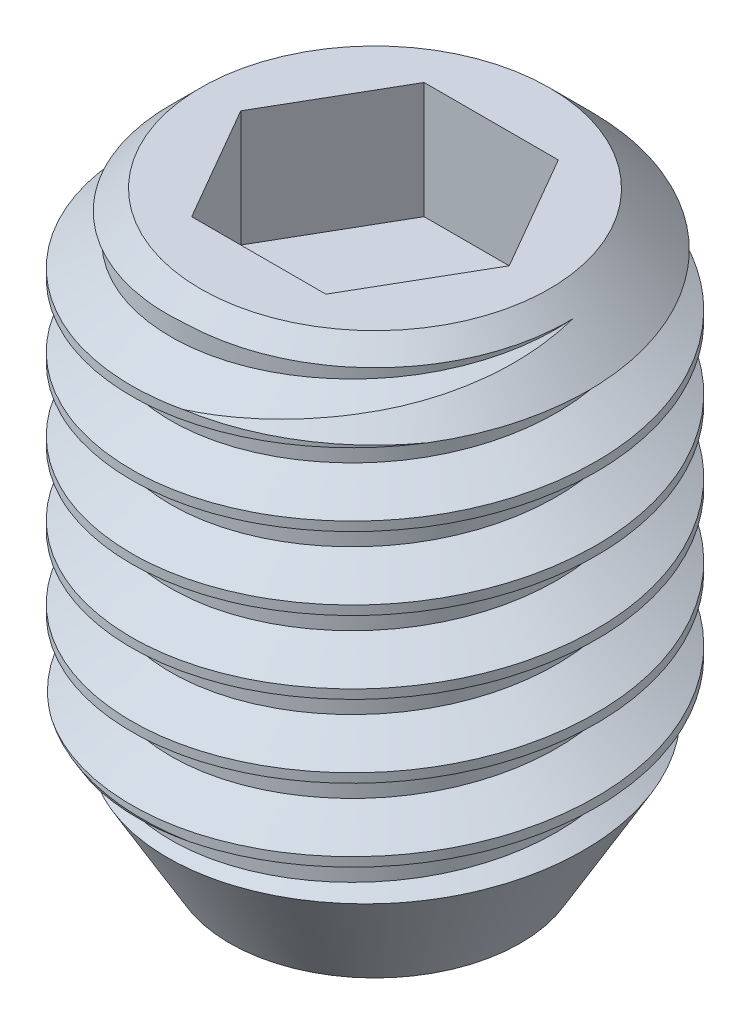
SolidWorks part; units mm, degrees
material "AISI 1020"
ref_plane "Front Plane" through (0, 0, 0) normal (0, 0, 1) x (1, 0, 0)
ref_plane "Top Plane" through (0, 0, 0) normal (0, 1, 0) x (1, 0, 0)
ref_plane "Right Plane" through (0, 0, 0) normal (1, 0, 0) x (0, 0, -1)
sketch "Sketch2" plane through (0, 0, 0) normal (0, 0, 1) x (1, 0, 0)
  line L0 (0, 0) -> (0, 10) construction
  line L1 (0, 10) -> (3, 10)
  line L2 (4, 9) -> (4, 2.5981)
  line L3 (4, 2.5981) -> (2.5, 0)
  line L4 (2.5, 0) -> (0, 0)
  line L5 (3, 10) -> (4, 9)
  line L6 (0, 0) -> (0, 10)
  point P4 (4, 10)
  dimension "D1" = 10
  dimension "D2" = 5
  dimension "D3" = 8
  dimension "D4" = 60
revolve "Revolve1" add sketch "Sketch2" angle 360 about L0
sketch "Sketch3" plane through (0, 10, 0) normal (0, 1, 0) x (1, 0, 0)
  line L1 (2.3094, 0) -> (1.1547, 2)
  line L2 (1.1547, 2) -> (-1.1547, 2)
  line L3 (-1.1547, 2) -> (-2.3094, 0)
  line L4 (-2.3094, 0) -> (-1.1547, -2)
  line L5 (-1.1547, -2) -> (1.1547, -2)
  line L6 (1.1547, -2) -> (2.3094, 0)
  circle A0 centre (0, 0) radius 2 construction
  circle A1 centre (0, 0) radius 3 construction
  dimension "D1" = 1
extrude "Cut-Extrude1" cut sketch "Sketch3" against normal blind 2
thread "Thread1" pitch 1.25 method cut profile "Thread Profile1" start angle 0, offset 2, length 0, pitch 1.25, diameter 8
ref_plane "Plane1" through (-4, 11, 0) normal (0, 0, 1) x (-1, 0, 0)
sketch "Thread Profile1" plane through (-4, 11, 0) normal (0, 0, 1) x (-1, 0, 0)
  line L0 (0, 0) -> (0, 1.25) construction
  line L11 (0, 0) -> (0, 1.0937)
  line L12 (0, 1.0937) -> (-0.6766, 0.7031)
  line L13 (-0.6766, 0.7031) -> (-0.6766, 0.3906)
  line L15 (-0.6766, 0.3906) -> (0, 0)
  line L17 (-0.6766, 0.5469) -> (0, 0.5469) construction
  point P2 (0, 0)
  dimension "Pitch" = 1.25
  dimension "Profile_Angle" = 60
  dimension "Profile_Land" = 0.3125
  dimension "Profile_Height" = 0.6766
